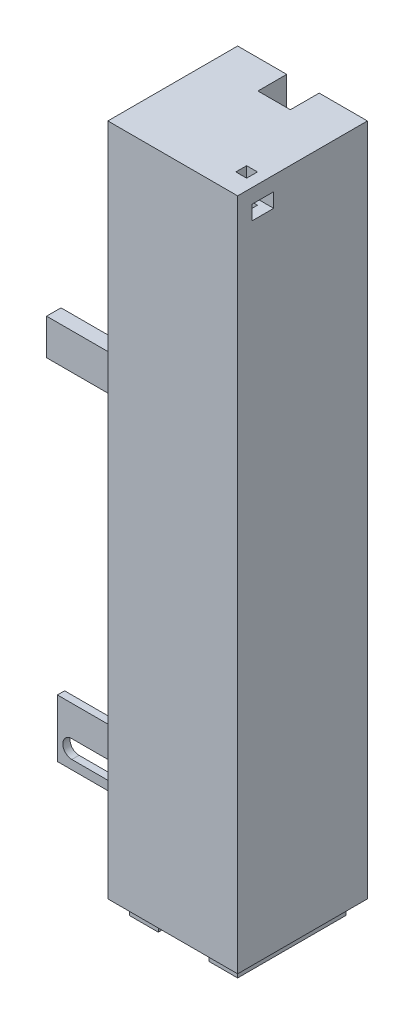
SolidWorks part; units mm, degrees
ref_plane "Front Plane" through (0, 0, 0) normal (0, 0, 1) x (1, 0, 0)
ref_plane "Top Plane" through (0, 0, 0) normal (0, 1, 0) x (1, 0, 0)
ref_plane "Right Plane" through (0, 0, 0) normal (1, 0, 0) x (0, 0, -1)
sketch "Sketch1" plane through (0, 0, 0) normal (0, 1, 0) x (1, 0, 0)
  line L1 (0, 0) -> (36, 0)
  line L2 (0, 0) -> (0, 36)
  line L3 (0, 36) -> (36, 36)
  line L4 (36, 0) -> (36, 36)
  dimension "D1" = 36
  dimension "D2" = 36
extrude "Boss-Extrude1" add sketch "Sketch1" along normal blind 186.9
sketch "Sketch2" plane through (0, 0, 0) normal (0, -1, 0) x (1, 0, 0)
  line L0 (0, 0) -> (36, 0) construction
  line L1 (3, -3) -> (7, -3)
  line L2 (3, -3) -> (3, -33)
  line L3 (3, -33) -> (7, -33)
  line L4 (7, -11) -> (7, -25)
  line L5 (36, -36) -> (0, -36) construction
  line L6 (0, -36) -> (0, 0) construction
  line L20 (36, 0) -> (36, -36) construction
  line L29 (7, -3) -> (11, -3)
  line L31 (7, -11) -> (11, -11)
  line L32 (11, -3) -> (11, -11)
  line L33 (7, -25) -> (11, -25)
  line L35 (7, -33) -> (11, -33)
  line L36 (11, -25) -> (11, -33)
  line L45 (29, -3) -> (33, -3)
  line L46 (29, -11) -> (29, -25)
  line L47 (29, -33) -> (33, -33)
  line L48 (33, -3) -> (33, -33)
  line L50 (29, -3) -> (25, -3)
  line L52 (29, -11) -> (25, -11)
  line L53 (25, -3) -> (25, -11)
  line L54 (29, -33) -> (25, -33)
  line L56 (29, -25) -> (25, -25)
  line L57 (25, -33) -> (25, -25)
  dimension "D1" = 3
  dimension "D2" = 3
  dimension "D3" = 3
  dimension "D4" = 4
  dimension "D5" = 4
  dimension "D6" = 8
  dimension "D7" = 8
  dimension "D8" = 4
  dimension "D9" = 3
  dimension "D10" = 3
  dimension "D11" = 3
  dimension "D12" = 4
  dimension "D13" = 4
  dimension "D14" = 4
extrude "Boss-Extrude2" add sketch "Sketch2" along normal blind 4
sketch "Sketch3" plane through (0, 0, 0) normal (0, -1, 0) x (1, 0, 0)
  line L0 (36, -36) -> (0, -36) construction
  line L2 (0, -36) -> (0, 0) construction
  circle A0 centre (18, -18) radius 2
  dimension "D1" = 4
  dimension "D2" = 18
  dimension "D3" = 18
extrude "Cut-Extrude1" cut sketch "Sketch3" against normal blind 5
sketch "Sketch4" plane through (0, 0, -36) normal (0, 0, 1) x (1, 0, 0)
  line L0 (0, 186.9) -> (36, 186.9) construction
  line L1 (13.62, 186.9) -> (22.62, 186.9)
  line L2 (13.62, 186.9) -> (13.62, 0)
  line L3 (13.62, 0) -> (22.62, 0)
  line L4 (22.62, 186.9) -> (22.62, 0)
  line L5 (0, 0) -> (36, 0) construction
  line L7 (36, 186.9) -> (36, 0) construction
  dimension "D1" = 13.38
  dimension "D2" = 9
extrude "Cut-Extrude2" cut sketch "Sketch4" along normal blind 8
sketch "Sketch5" plane through (36, 0, 0) normal (1, 0, 0) x (0, 0, -1)
  line L0 (0, 186.9) -> (36, 186.9) construction
  line L1 (4, 182.9) -> (10, 182.9)
  line L2 (4, 182.9) -> (4, 178.9)
  line L3 (4, 178.9) -> (10, 178.9)
  line L4 (10, 182.9) -> (10, 178.9)
  line L5 (0, 186.9) -> (0, 0) construction
  dimension "D1" = 6
  dimension "D2" = 4
  dimension "D3" = 4
  dimension "D4" = 4
extrude "Cut-Extrude3" cut sketch "Sketch5" against normal blind 9
sketch "Sketch6" plane through (0, 186.9, 0) normal (0, 1, 0) x (1, 0, 0)
  line L0 (36, 0) -> (36, 36) construction
  line L1 (30, 8.5) -> (33, 8.5)
  line L2 (30, 8.5) -> (30, 5.5)
  line L3 (30, 5.5) -> (33, 5.5)
  line L4 (33, 8.5) -> (33, 5.5)
  line L5 (0, 0) -> (36, 0) construction
  dimension "D1" = 3
  dimension "D2" = 3
  dimension "D3" = 3
  dimension "D4" = 5.5
extrude "Cut-Extrude4" cut sketch "Sketch6" against normal blind 10
sketch "Sketch7" plane through (0, 0, 0) normal (-1, 0, 0) x (0, 0, 1)
  line L0 (-36, 186.9) -> (-36, 0) construction
  line L1 (-28, 0) -> (-26, 0)
  line L2 (-28, 0) -> (-28, 16)
  line L3 (-28, 16) -> (-26, 16)
  line L4 (-26, 0) -> (-26, 16)
  dimension "D1" = 2
  dimension "D2" = 16
  dimension "D3" = 8
extrude "Boss-Extrude3" add sketch "Sketch7" along normal blind 40
sketch "Sketch8" plane through (0, 0, -26) normal (0, 0, 1) x (1, 0, 0)
  line L0 (-40, 0) -> (0, 0) construction
  line L1 (-40, 0) -> (-40, 16) construction
  line L3 (-36, 7.5) -> (-12, 7.5)
  line L5 (-36, 2.5) -> (-12, 2.5)
  arc A0 (-36, 7.5) -> (-36, 2.5) centre (-36, 5) ccw
  arc A1 (-12, 2.5) -> (-12, 7.5) centre (-12, 5) ccw
  dimension "D1" = 5
  dimension "D2" = 5
  dimension "D4" = 5
  dimension "D3" = 4
  dimension "D5" = 5
  dimension "D6" = 24
extrude "Cut-Extrude5" cut sketch "Sketch8" against normal up to next
sketch "Sketch9" plane through (0, 0, 0) normal (-1, 0, 0) x (0, 0, 1)
  line L0 (-26, 0) -> (0, 0) construction
  line L1 (-32, 103.5) -> (-28, 103.5)
  line L2 (-32, 103.5) -> (-32, 93.5)
  line L3 (-32, 93.5) -> (-28, 93.5)
  line L4 (-28, 103.5) -> (-28, 93.5)
  line L5 (-36, 186.9) -> (-36, 0) construction
  dimension "D1" = 103.5
  dimension "D2" = 10
  dimension "D3" = 4
  dimension "D4" = 4
extrude "Boss-Extrude4" add sketch "Sketch9" along normal blind 45
chamfer "Chamfer1" distance 20 angle 45 2 edges at (0, 93.5, -30) (0, 16, -27)
sketch "Sketch10" plane through (0, 0, -26) normal (0, 0, 1) x (1, 0, 0)
  line L0 (-17.1716, 93.5) -> (-2, 78.3284)
  line L1 (-2, 78.3284) -> (-2, 93.5)
  line L2 (-2, 93.5) -> (-17.1716, 93.5)
  line L3 (0, 186.9) -> (0, 0) construction
  line L4 (-20, 93.5) -> (0, 73.5) construction
  line L5 (-45, 93.5) -> (-20, 93.5) construction
  line L6 (-17.1716, 16) -> (-2, 31.1716)
  line L7 (-2, 31.1716) -> (-2, 16)
  line L8 (-2, 16) -> (-17.1716, 16)
  line L9 (0, 36) -> (-20, 16) construction
  line L10 (-40, 16) -> (-20, 16) construction
  dimension "D1" = 2
  dimension "D2" = 2
  dimension "D3" = 0
  dimension "D4" = 2
  dimension "D5" = 2
  dimension "D6" = 0
extrude "Cut-Extrude6" cut sketch "Sketch10" along direction (0, 0, -1) on the side against the normal blind 27
